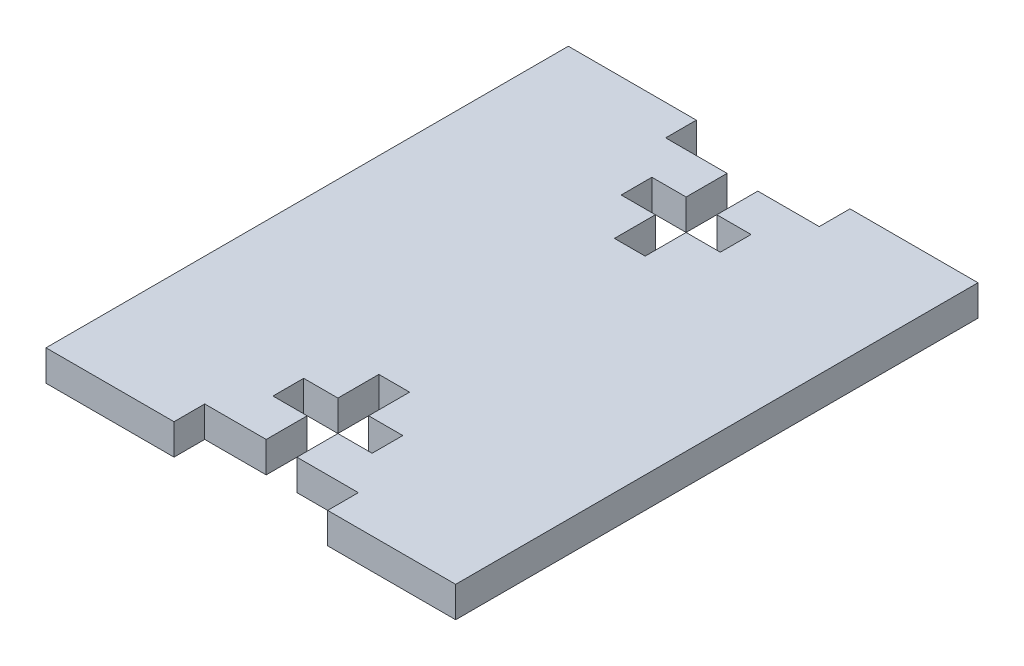
SolidWorks part; units mm, degrees
material "PVC rigido"
ref_plane "Piano frontale" through (0, 0, 0) normal (0, 0, 1) x (1, 0, 0)
ref_plane "Piano superiore" through (0, 0, 0) normal (0, 1, 0) x (1, 0, 0)
ref_plane "Piano destro" through (0, 0, 0) normal (1, 0, 0) x (0, 0, -1)
sketch "Schizzo1" plane through (0, 0, 0) normal (0, 1, 0) x (1, 0, 0)
  line L1 (-54.5649, -28.2811) -> (-14.5649, -28.2811)
  line L2 (-54.5649, -28.2811) -> (-54.5649, 22.7189)
  line L3 (-54.5649, 22.7189) -> (-14.5649, 22.7189)
  line L4 (-14.5649, -28.2811) -> (-14.5649, 22.7189)
  dimension "D1" = 40
  dimension "D2" = 51
sketch "Schizzo2" plane through (0, 0, 0) normal (0, 1, 0) x (1, 0, 0)
  line L0 (-54.5649, -2.7811) -> (-14.5649, -2.7811) construction
  line L5 (-54.5649, -28.2811) -> (-54.5649, 22.7189) construction
  line L6 (-14.5649, -28.2811) -> (-14.5649, 22.7189) construction
  line L7 (-34.5649, -28.2811) -> (-34.5649, 22.7189) construction
  line L8 (-54.5649, -28.2811) -> (-14.5649, -28.2811) construction
  line L9 (-54.5649, 22.7189) -> (-14.5649, 22.7189) construction
  line L22 (-42.0649, -28.2811) -> (-27.0649, -28.2811)
  line L23 (-42.0649, -28.2811) -> (-42.0649, -25.2811)
  line L24 (-42.0649, -25.2811) -> (-27.0649, -25.2811)
  line L25 (-27.0649, -28.2811) -> (-27.0649, -25.2811)
  line L26 (-42.0649, 22.7189) -> (-42.0649, 19.7189)
  line L27 (-42.0649, 19.7189) -> (-27.0649, 19.7189)
  line L28 (-27.0649, 22.7189) -> (-27.0649, 19.7189)
  line L29 (-42.0649, 22.7189) -> (-27.0649, 22.7189)
  point P33 (-34.5649, -25.2811)
  dimension "D3" = 15
  dimension "D4" = 3
extrude "Estrusione-Estrusione2" add sketch "Schizzo1" against normal blind 3
extrude "Taglio-Estrusione1" cut sketch "Schizzo2" against normal through all
sketch "Schizzo3" plane through (0, 0, 0) normal (0, 1, 0) x (1, 0, 0)
  line L1 (-36.0649, -25.2811) -> (-33.0649, -25.2811)
  line L2 (-54.5649, -2.7811) -> (-14.5649, -2.7811) construction
  line L3 (-54.5649, 22.7189) -> (-54.5649, -28.2811) construction
  line L15 (-14.5649, -28.2811) -> (-14.5649, 22.7189) construction
  line L19 (-34.5649, 19.7189) -> (-34.5649, -25.2811) construction
  line L20 (-42.0649, 19.7189) -> (-27.0649, 19.7189) construction
  line L21 (-27.0649, -25.2811) -> (-42.0649, -25.2811) construction
  line L26 (-36.0649, -25.2811) -> (-36.0649, -21.2811)
  line L27 (-36.0649, -21.2811) -> (-39.4049, -21.2811)
  line L28 (-39.4049, -21.2811) -> (-39.4049, -18.2811)
  line L29 (-39.4049, -18.2811) -> (-36.0649, -18.2811)
  line L30 (-36.0649, -18.2811) -> (-36.0649, -14.2811)
  line L31 (-36.0649, -14.2811) -> (-33.0649, -14.2811)
  line L32 (-33.0649, -14.2811) -> (-33.0649, -18.2811)
  line L33 (-33.0649, -18.2811) -> (-29.7249, -18.2811)
  line L34 (-29.7249, -18.2811) -> (-29.7249, -21.2811)
  line L35 (-29.7249, -21.2811) -> (-33.0649, -21.2811)
  line L36 (-33.0649, -21.2811) -> (-33.0649, -25.2811)
  line L60 (-36.0649, 8.7189) -> (-33.0649, 8.7189)
  line L61 (-36.0649, 12.7189) -> (-36.0649, 8.7189)
  line L62 (-39.4049, 12.7189) -> (-36.0649, 12.7189)
  line L63 (-39.4049, 15.7189) -> (-39.4049, 12.7189)
  line L64 (-36.0649, 15.7189) -> (-39.4049, 15.7189)
  line L65 (-36.0649, 19.7189) -> (-36.0649, 15.7189)
  line L66 (-36.0649, 19.7189) -> (-33.0649, 19.7189)
  line L67 (-33.0649, 15.7189) -> (-33.0649, 19.7189)
  line L68 (-29.7249, 15.7189) -> (-33.0649, 15.7189)
  line L69 (-29.7249, 12.7189) -> (-29.7249, 15.7189)
  line L70 (-33.0649, 12.7189) -> (-29.7249, 12.7189)
  line L71 (-33.0649, 8.7189) -> (-33.0649, 12.7189)
  point P53 (-34.5649, -25.2811)
  dimension "D8" = 3
  dimension "D9" = 4
  dimension "D10" = 4
  dimension "D11" = 3
  dimension "D12" = 3.34
extrude "Taglio-Estrusione3" cut sketch "Schizzo3" against normal through all
equation "\"Thickness2\"=3"
equation "\"Thickness3\"=3"
equation "\"D4@Schizzo2\"=\"Thickness3\""
equation "\"D1@Estrusione-Estrusione2\"=\"Thickness2\""
equation "\"D2@Schizzo1\"=\"Thickness2\"*2+45"
